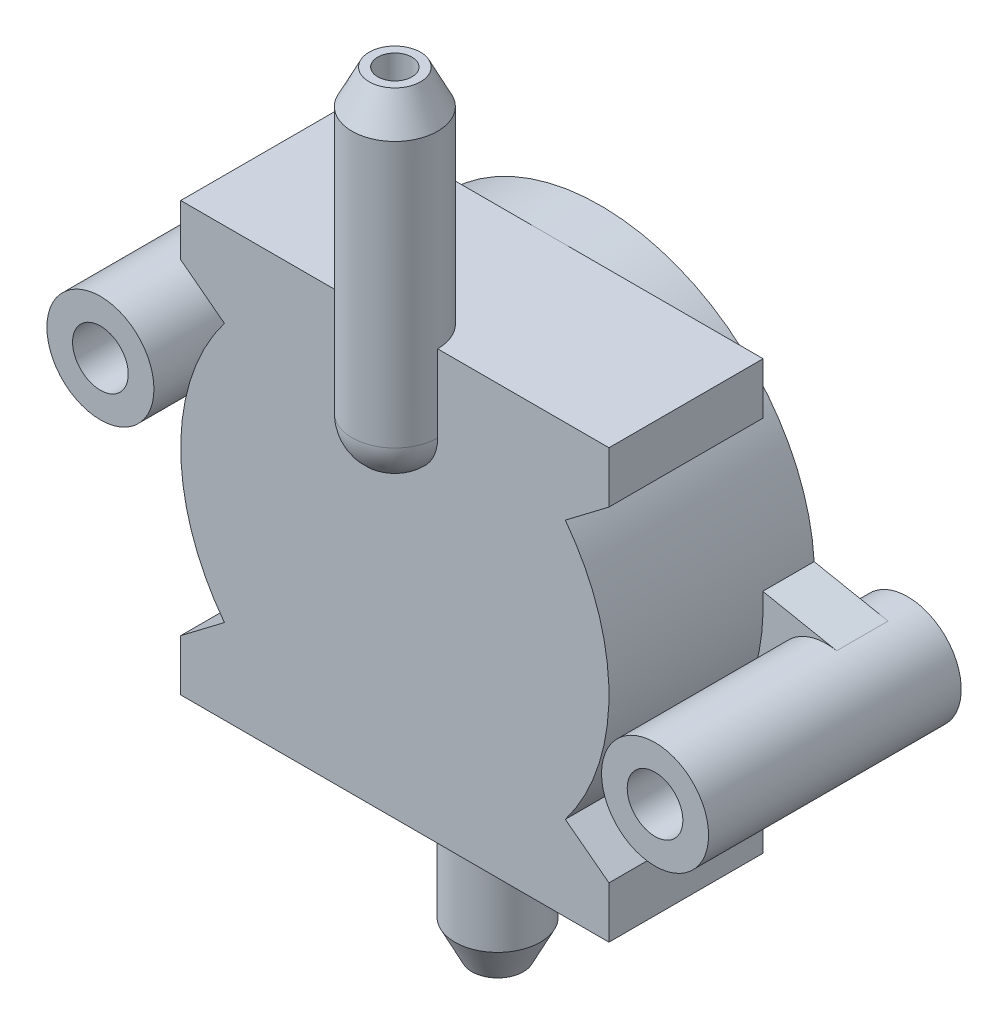
SolidWorks part; units mm, degrees
ref_plane "Alzado" through (0, 0, 0) normal (0, 0, 1) x (1, 0, 0)
ref_plane "Planta" through (0, 0, 0) normal (0, 1, 0) x (1, 0, 0)
ref_plane "Vista lateral" through (0, 0, 0) normal (1, 0, 0) x (0, 0, -1)
sketch "Croquis2" plane through (0, 0, 0) normal (0, 0, 1) x (1, 0, 0)
  line L0 (-12.5, 12.5) -> (12.5, 12.5)
  line L1 (12.5, 12.5) -> (12.5, 9.5)
  line L2 (12.5, 9.5) -> (9.952, 7.5635)
  line L3 (0, 12.5) -> (0, -12.5) construction
  line L4 (12.5, 19.8599) -> (12.5, -19.8599) construction
  line L5 (-12.5, 0) -> (12.5, 0) construction
  line L6 (-12.5, 9.5) -> (-9.952, 7.5635)
  line L7 (-12.5, 12.5) -> (-12.5, 9.5)
  line L8 (12.5, -9.5) -> (9.952, -7.5635)
  line L9 (12.5, -12.5) -> (12.5, -9.5)
  line L10 (-12.5, -12.5) -> (12.5, -12.5)
  line L11 (-12.5, -12.5) -> (-12.5, -9.5)
  line L12 (-12.5, -9.5) -> (-9.952, -7.5635)
  arc A1 (9.952, -7.5635) -> (9.952, 7.5635) centre (0, 0) ccw
  arc A2 (-9.952, -7.5635) -> (-9.952, 7.5635) centre (0, 0) cw
  dimension "D1" = 12.5
  dimension "D2" = 3
  dimension "D3" = 12.5
extrude "Saliente-Extruir1" add sketch "Croquis2" along normal blind 9
sketch "Croquis3" plane through (0, 0, 0) normal (0, 0, -1) x (-1, 0, 0)
  circle A0 centre (0, 0) radius 1.3441
extrude "Saliente-Extruir2" add sketch "Croquis3" along normal blind 1
sketch "Croquis4" plane through (0, 0, 0) normal (0, 0, -1) x (-1, 0, 0)
  circle A0 centre (0, 0) radius 12.5
  circle A3 centre (0, 0) radius 1.4441
  circle A4 centre (0, 0) radius 1.4441
  dimension "D1" = 0.1
extrude "Saliente-Extruir3" add sketch "Croquis4" along normal blind 3 separate body
sketch "Croquis5" plane through (0, 0, -3) normal (0, 0, -1) x (-1, 0, 0)
  circle A0 centre (0, 0) radius 1.4441 construction
  circle A1 centre (0, 0) radius 1.4441
extrude "Saliente-Extruir4" add sketch "Croquis5" against normal up to surface (2 mm away) up to face at (-1.3441, 0, -1)
sketch "Croquis6" plane through (0, 0, -3) normal (0, 0, -1) x (-1, 0, 0)
  line L0 (-16.1897, -3.1849) -> (16.1897, 3.1849) construction
  line L1 (-16.7929, -0.1187) -> (-12.4787, 0.73)
  line L2 (15.5865, 6.2511) -> (11.2723, 5.4024)
  line L3 (-15.5865, -6.2511) -> (-11.2723, -5.4024)
  line L4 (16.7929, 0.1187) -> (12.4787, -0.73)
  line L5 (16.7929, 0.1187) -> (15.5865, 6.2511) construction
  line L6 (-15.5865, -6.2511) -> (-16.7929, -0.1187) construction
  line L7 (0, 0) -> (-16.1897, 3.1849) construction
  line L8 (-16.1897, -3.1849) -> (-16.1897, 3.1849) construction
  line L9 (-16.1897, 0) -> (0, 0) construction
  circle A0 centre (-16.1897, -3.1849) radius 1.625
  circle A1 centre (16.1897, 3.1849) radius 1.625
  arc A2 (-16.7929, -0.1187) -> (-15.5865, -6.2511) centre (-16.1897, -3.1849) ccw
  arc A3 (16.7929, 0.1187) -> (15.5865, 6.2511) centre (16.1897, 3.1849) ccw
  circle A4 centre (0, 0) radius 12.5 construction
  arc A5 (12.4787, -0.73) -> (11.2723, 5.4024) centre (0, 0) ccw
  circle A6 centre (-16.1897, -3.1849) radius 3.125 construction
  circle A7 centre (16.1897, 3.1849) radius 3.125 construction
  circle A9 centre (-16.1897, 3.1849) radius 3.125 construction
  point P2 (0, 0)
  point P22 (16.1897, 3.1849)
  point P24 (-16.1897, -3.1849)
  point P27 (-16.1897, 0)
  circle M8 centre (0, 0) radius 12.5
  dimension "D2" = 3.25
  dimension "D1" = 33
  dimension "D3" = 1.5
  dimension "D4" = 1.5
extrude "Saliente-Extruir5" add sketch "Croquis6" against normal up to vertex (3 mm away) contours L1 A2 L3 A0 M8 | L4 A3 L2 A1 M8 region at (14.6152, 0.2008, -3) region at (-13.45, 5.7219, -3) up to point (9.952, 7.5635, 0)
sketch "Croquis7" plane through (0, 0, -3) normal (0, 0, -1) x (-1, 0, 0)
  line L0 (-16.7929, -0.1187) -> (-15.5865, -6.2511) construction
  line L1 (15.5865, 6.2511) -> (16.7929, 0.1187) construction
  arc A0 (-16.7929, -0.1187) -> (-15.5865, -6.2511) centre (-16.1897, -3.1849) ccw construction
  circle A1 centre (-16.1897, -3.1849) radius 3.125
  circle A2 centre (-16.1897, -3.1849) radius 1.625 construction
  circle A3 centre (16.1897, 3.1849) radius 1.625 construction
  arc A4 (16.7929, 0.1187) -> (15.5865, 6.2511) centre (16.1897, 3.1849) ccw construction
  circle A5 centre (-16.1897, -3.1849) radius 1.625
  circle A6 centre (16.1897, 3.1849) radius 1.625
  circle A7 centre (16.1897, 3.1849) radius 3.125
extrude "Saliente-Extruir6" add sketch "Croquis7" along normal blind 1.75
sketch "Croquis8" plane through (0, 0, 0) normal (0, 0, 1) x (1, 0, 0)
  circle A0 centre (-16.1897, 3.1849) radius 3.125 construction
  circle A1 centre (-16.1897, 3.1849) radius 1.625 construction
  circle A2 centre (16.1897, -3.1849) radius 1.625 construction
  circle A3 centre (16.1897, -3.1849) radius 3.125 construction
  circle A4 centre (-16.1897, 3.1849) radius 3.125
  circle A5 centre (-16.1897, 3.1849) radius 1.625
  circle A6 centre (16.1897, -3.1849) radius 1.625
  circle A7 centre (16.1897, -3.1849) radius 3.125
extrude "Saliente-Extruir7" add sketch "Croquis8" along normal blind 10
sketch "Croquis9" plane through (0, 12.5, 0) normal (0, 1, 0) x (1, 0, 0)
  line L0 (12.5, -9) -> (-12.5, -9) construction
  circle A0 centre (0, -9) radius 2.5
  dimension "D1" = 5
extrude "Saliente-Extruir8" add sketch "Croquis9" along normal blind 13 and the other way blind 7
fillet "Redondeo1" radius 2.5 1 edges at (0, 5.5, 11.5)
sketch "Croquis11" plane through (0, -12.5, 0) normal (0, -1, 0) x (1, 0, 0)
  line L0 (12.5, 0.5) -> (-12.5, 0.5) construction
  line L1 (12.5, 9) -> (12.5, 0) construction
  line L2 (-12.5, 9) -> (-12.5, 0) construction
  line L3 (-12.4787, -3) -> (11.2723, -3) construction
  line L4 (0, 9) -> (0, -3) construction
  circle A0 centre (0, 3) radius 2.5
  circle A1 centre (0, 3) radius 1
  point P14 (0, -3)
  point P15 (0, 3)
  dimension "D2" = 5
  dimension "D3" = 2
  dimension "D1" = 3.5
extrude "Saliente-Extruir9" add sketch "Croquis11" along normal blind 10
chamfer "Chaflán1" distance 2 distance2 1 2 edges at (0, 25.5, 11.5) (0, -22.5, 0.5) first distance on face at (0, 25.5, 11.5) first distance on face at (0, -22.5, 0.5)
sketch "Croquis10" plane through (0, 25.5, 0) normal (0, 1, 0) x (1, 0, 0)
  circle A0 centre (0, -9) radius 1
  circle A1 centre (0, -9) radius 1.5 construction
  dimension "D1" = 2
extrude "Cortar-Extruir1" cut sketch "Croquis10" against normal blind 15
